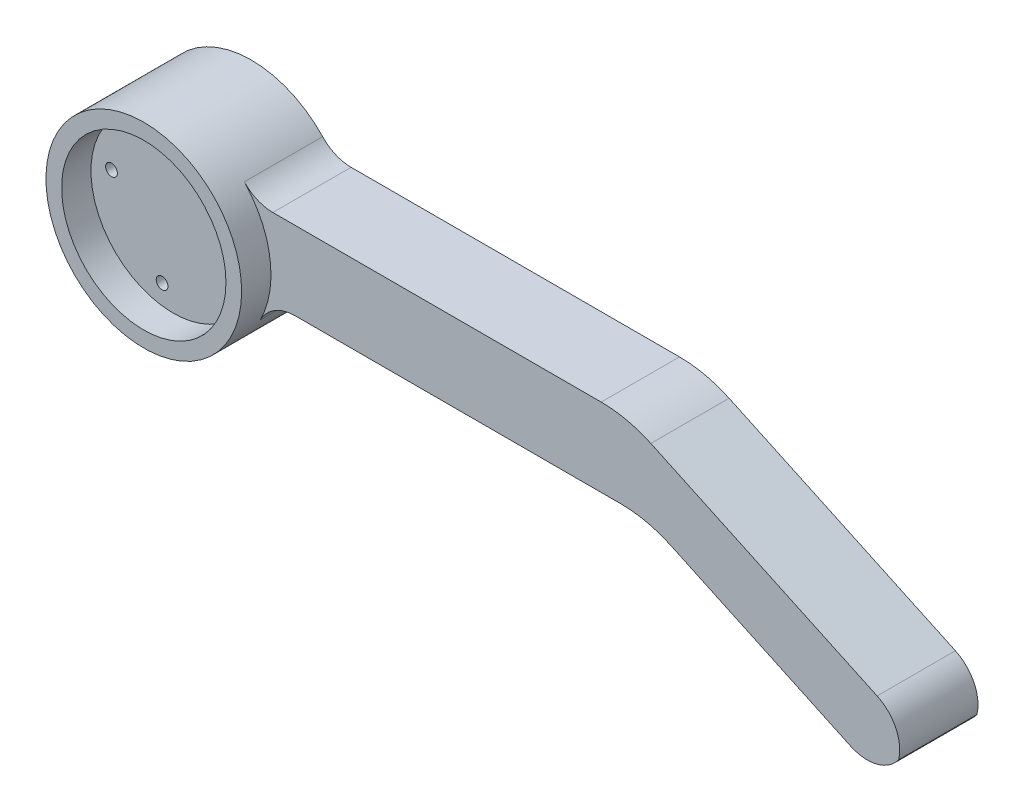
SolidWorks part; units mm, degrees
material "ABS"
ref_plane "Front" through (0, 0, 0) normal (0, 0, 1) x (1, 0, 0)
ref_plane "Top" through (0, 0, 0) normal (0, 1, 0) x (1, 0, 0)
ref_plane "Right" through (0, 0, 0) normal (1, 0, 0) x (0, 0, -1)
sketch "Esquisse1" plane through (0, 0, 0) normal (0, 0, 1) x (1, 0, 0)
  line L2 (10.3562, 7) -> (58.0156, 7)
  line L3 (12.1347, -3) -> (60.5311, -3)
  line L4 (58.0156, 7) -> (94.4722, -10)
  line L5 (94.4722, -10) -> (91.0913, -17.2505)
  line L6 (91.0913, -17.2505) -> (60.5311, -3)
  arc A0 (10.3562, 7) -> (12.1347, -3) centre (0, 0) ccw
  circle A2 centre (0, 0) radius 95 construction
  dimension "D1" = 12.5
  dimension "D4" = 10
  dimension "D5" = 7
  dimension "D9" = 190
  dimension "D2" = 10
  dimension "D3" = 8
  dimension "D8" = 25
extrude "Boss.-Extru.1" add sketch "Esquisse1" along normal mid plane 10
fillet "Congé4" radius 5 2 edges at (12.1347, -3, 0) (10.3562, 7, 0)
fillet "Congé3" radius 15 2 edges at (60.5311, -3, 0) (58.0156, 7, 0)
sketch "Esquisse10" plane through (0, 0, 0) normal (0, 1, 0) x (1, 0, 0)
  line L0 (0.6976, 9.9756) -> (-0.6976, -9.9756)
  line L1 (-50, 0) -> (50, 0) construction
  line L2 (0.6976, 9.9756) -> (3.79, 9.7594)
  line L3 (3.79, 9.7594) -> (2.3949, -10.1919)
  line L4 (2.3949, -10.1919) -> (-0.6976, -9.9756)
  line L5 (0.6976, 9.9756) -> (0.9138, 13.0681) construction
  dimension "D1" = 86
  dimension "D2" = 20
  dimension "D3" = 6.2
revolve "Enlèvement de matière-Révolution1" [suppressed] cut sketch "Esquisse10" angle 360 about L5
sketch "Esquisse13" plane through (0, 0, 0) normal (0, 0, 1) x (1, 0, 0)
  line L0 (1.9, -9) -> (1.9, -12.5)
  line L1 (0, 12.5) -> (3, 12.5)
  line L2 (0, 12.5) -> (0, -12.5)
  line L3 (0, -12.5) -> (1.9, -12.5)
  line L4 (3, 12.5) -> (3, 9.5)
  line L5 (1.9, -9) -> (1.55, -9)
  line L7 (3, 9.5) -> (1.55, 9.5)
  line L8 (1.55, -9) -> (1.55, 9.5)
  line L9 (0, 12.5) -> (0, 15.5) construction
  arc A0 (9.0984, 8.5714) -> (11.1174, -5.7143) centre (0, 0) ccw construction
  dimension "D1" = 6
  dimension "D2" = 3.8
  dimension "D3" = 3.1
  dimension "D4" = 3.5
  dimension "D5" = 3
revolve "Enlèvement de matière-Révolution5" [suppressed] cut sketch "Esquisse13" angle 360 about L9
sketch "Esquisse7" plane through (0, 0, 5) normal (0, 0, 1) x (1, 0, 0)
  circle A0 centre (0, 0) radius 12.5
  arc A2 (9.0984, 8.5714) -> (11.1174, -5.7143) centre (0, 0) ccw construction
extrude "Boss.-Extru.2" [suppressed] add sketch "Esquisse7" against normal blind 0.2
fillet "Congé5" [suppressed] radius 5
sketch "Esquisse8" plane through (0, 0, -5) normal (0, 0, -1) x (-1, 0, 0)
  line L0 (-20.7144, 0.95) -> (-20.7144, -0.15)
  line L3 (-54.6902, 7) -> (-12.7377, 7) construction
  line L4 (-15.5644, -3) -> (-57.2056, -3) construction
  line L5 (-23.5644, -3) -> (-15.5644, -3)
  line L6 (-18.4144, -0.15) -> (-18.4144, 0.95)
  line L8 (-23.5644, 5) -> (-15.5644, 5)
  line L9 (-15.5644, 5) -> (-15.5644, -1)
  line L10 (-16.4144, -0.15) -> (-16.4144, 0.95)
  line L11 (-22.7144, 0.95) -> (-22.7144, -0.15)
  line L12 (-23.5644, -1) -> (-31.5644, -1)
  line L13 (-31.5644, -1) -> (-31.5644, 5)
  line L14 (-30.7144, 4.15) -> (-30.7144, 3.05)
  line L15 (-24.4144, 3.05) -> (-24.4144, 4.15)
  line L16 (-31.5644, 7) -> (-23.5644, 7)
  line L17 (-28.7144, 4.15) -> (-28.7144, 3.05)
  line L18 (-26.4144, 3.05) -> (-26.4144, 4.15)
  arc A2 (-20.7144, -0.15) -> (-23.5644, -3) centre (-23.5644, -0.15) cw
  arc A3 (-15.5644, -3) -> (-18.4144, -0.15) centre (-15.5644, -0.15) cw
  arc A4 (-18.4144, 0.95) -> (-20.7144, 0.95) centre (-19.5644, 0.95) ccw
  arc A5 (-15.5644, -1) -> (-16.4144, -0.15) centre (-15.5644, -0.15) cw
  arc A6 (-16.4144, 0.95) -> (-22.7144, 0.95) centre (-19.5644, 0.95) ccw
  arc A7 (-22.7144, -0.15) -> (-23.5644, -1) centre (-23.5644, -0.15) cw
  arc A8 (-31.5644, 5) -> (-30.7144, 4.15) centre (-31.5644, 4.15) cw
  arc A9 (-30.7144, 3.05) -> (-24.4144, 3.05) centre (-27.5644, 3.05) ccw
  arc A10 (-24.4144, 4.15) -> (-23.5644, 5) centre (-23.5644, 4.15) cw
  arc A11 (-31.5644, 7) -> (-28.7144, 4.15) centre (-31.5644, 4.15) cw
  arc A12 (-28.7144, 3.05) -> (-26.4144, 3.05) centre (-27.5644, 3.05) ccw
  arc A13 (-26.4144, 4.15) -> (-23.5644, 7) centre (-23.5644, 4.15) cw
  dimension "D1" = 2.3
  dimension "D2" = 2
  dimension "D3" = 2
  dimension "D4" = 8
  dimension "D5" = 0.9
  dimension "D6" = 39.1258
  dimension "D7" = 16
  dimension "D9" = 1.7
extrude "Enlèv. mat.-Extru.5" [suppressed] cut sketch "Esquisse8" against normal through all and the other way through all
pattern_linear "Répétition linéaire1" [suppressed] count 3 spacing 16 of bodies 113
fillet "Congé6" radius 5 2 edges at (94.4722, -10, 0) (91.0913, -17.2505, 0) tangent propagation no
sketch "Esquisse15" plane through (0, 0, 0) normal (0, 1, 0) x (1, 0, 0)
  line L0 (0, 5) -> (0, -5) construction
  line L1 (150, 5) -> (8.5, 5)
  line L2 (150, 5) -> (150, 1)
  line L3 (150, 1) -> (50, 1)
  line L5 (-12.5, -5) -> (11.1174, -5) construction
  line L6 (11.1174, 5) -> (-12.5, 5) construction
  line L7 (89.9407, -5) -> (61.0295, -5) construction
  ellipse E0 centre (50, 5) end of major axis (8.5, 5) minor radius 4 (8.5, 5) -> (50, 1) ccw
  dimension "D1" = 6
  dimension "D2" = 17
  dimension "D3" = 50
  dimension "D4" = 150
revolve "Enlèvement de matière-Révolution6" [suppressed] cut sketch "Esquisse15" angle 360 about L0
fillet "Congé7" [suppressed] radius 1
sketch "Sketch1" [suppressed] plane through (0, 0, 0) normal (0, 0, 1) x (1, 0, 0)
  circle A0 centre (0, 0) radius 10.375
  dimension "D1" = 20.75
extrude "Cut-Extrude2" [suppressed] cut sketch "Sketch1" against normal through all from offset 4 offset against normal yes
sketch "Sketch2" [suppressed] plane through (0, 0, 0) normal (1, 0, 0) x (0, 0, -1)
  line L1 (3.8113, -10.375) -> (6.8474, -10.375)
  line L2 (3.8113, -10.375) -> (3.8113, 13.3524)
  line L3 (3.8113, 13.3524) -> (6.8474, 13.3524)
  line L4 (6.8474, -10.375) -> (6.8474, 13.3524)
extrude "Cut-Extrude3" [suppressed] cut sketch "Sketch2" against normal through all and the other way blind 10
sketch "Sketch3" [suppressed] plane through (0, 0, -3.8113) normal (0, 0, -1) x (-1, 0, 0)
  circle A0 centre (-5.7385, -6.5818) radius 0.75
  circle A1 centre (-7.2335, -3.4171) radius 0.75
  circle A2 centre (-8.7285, -0.2525) radius 0.75
  circle A3 centre (-6.5818, 5.7385) radius 0.75
  circle A4 centre (-3.4171, 7.2335) radius 0.75
  circle A5 centre (-0.2525, 8.7285) radius 0.75
  circle A6 centre (0.2525, -8.7285) radius 0.75
  circle A7 centre (3.4171, -7.2335) radius 0.75
  circle A8 centre (6.5818, -5.7385) radius 0.75
  circle A9 centre (8.7285, 0.2525) radius 0.75
  circle A10 centre (7.2335, 3.4171) radius 0.75
  circle A11 centre (5.7385, 6.5818) radius 0.75
extrude "Cut-Extrude4" [suppressed] cut sketch "Sketch3" against normal through all
sketch "Sketch4" plane through (0, 0, -5) normal (0, 0, -1) x (-1, 0, 0)
  circle A0 centre (-1.4105, 7.8747) radius 0.75
  circle A1 centre (7.8747, 1.4105) radius 0.75
  circle A2 centre (1.4105, -7.8747) radius 0.75
  circle A3 centre (-7.8747, -1.4105) radius 0.75
  dimension "D1" = 1.5
  dimension "D2" = 4
extrude "Cut-Extrude5" cut sketch "Sketch4" against normal through all
sketch "Sketch5" plane through (0, 0, -5) normal (0, 0, -1) x (-1, 0, 0)
  circle A0 centre (0, 0) radius 10.5
  circle A1 centre (0, 0) radius 12.5
  dimension "D1" = 21
extrude "Boss-Extrude1" add sketch "Sketch5" against normal blind 3.75 from surface starting at face at (0.6605, 7.8747, 5)
equation "\"D3@Répétition linéaire1\"=\"D7@Esquisse8\""
